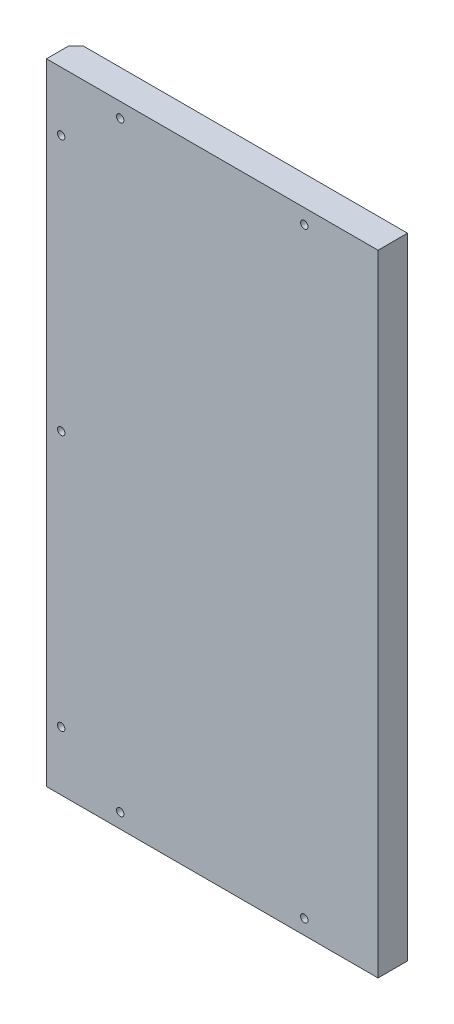
SolidWorks part; units mm, degrees
material "Beech"
ref_plane "Front Plane" through (0, 0, 0) normal (0, 0, 1) x (1, 0, 0)
ref_plane "Top Plane" through (0, 0, 0) normal (0, 1, 0) x (1, 0, 0)
ref_plane "Right Plane" through (0, 0, 0) normal (1, 0, 0) x (0, 0, -1)
sketch "Sketch1" plane through (0, 0, 0) normal (0, 0, 1) x (1, 0, 0)
  line L0 (-234.753, 19.05) -> (-234.753, 0) construction
  line L1 (-234.753, 82.8417) -> (-91.9973, 82.8417)
  line L2 (-234.753, 82.8417) -> (-234.753, -188.5238)
  line L3 (-234.753, -188.5238) -> (-91.9973, -188.5238)
  line L4 (-91.9973, 82.8417) -> (-91.9973, -188.5238)
extrude "Boss-Extrude1" add sketch "Sketch1" along normal blind 12.7
hole_wizard "Hole1" positions "Sketch2" profile "Sketch3" legacy
sketch "Sketch2" plane through (181.0394, -52.975, 0) normal (0, 0, -1) x (0, -1, 0)
  line L0 (-129.4667, 415.7924) -> (-129.4667, 273.0368) construction
  line L5 (-135.8167, 409.4424) -> (135.5488, 409.4424) construction
  line L10 (-135.8167, 279.3868) -> (135.5488, 279.3868) construction
  line L11 (-0.134, 409.4424) -> (-0.134, 279.3868) construction
  point P22 (-129.4667, 384.0424)
  point P24 (-129.4667, 304.7868)
  point P26 (-110.4167, 409.4424)
  point P30 (-0.134, 409.4424)
  point P50 (110.1488, 409.4424)
  point P51 (129.1988, 304.7868)
  point P52 (129.1988, 384.0424)
sketch "Sketch3" plane through (-203.003, -182.1738, 0) normal (1, 0, 0) x (0, 1, 0)
  line L0 (0, 0) -> (0, 32.7039)
  line L1 (0, 32.7039) -> (1.5875, 31.75)
  line L2 (1.5875, 31.75) -> (1.5875, 4.0177)
  line L3 (1.5875, 4.0177) -> (5.08, 0)
  line L4 (5.08, 0) -> (0, 0)
  line L5 (0, -14.3089) -> (0, 102.4216) construction
  line L6 (0, 32.7039) -> (-1.5875, 31.75) construction
  line L7 (-1.5875, 4.0177) -> (-5.08, 0) construction
  dimension "Diameter" = 3.175
  dimension "Depth" = 31.75
  dimension "C-Sink Diameter" = 10.16
  dimension "C-Sink Angle" = 82
  dimension "Drill Angle" = 118
chamfer "Chamfer1" distance 3.175 angle 45 1 edges at (-234.753, -52.841, 0)
